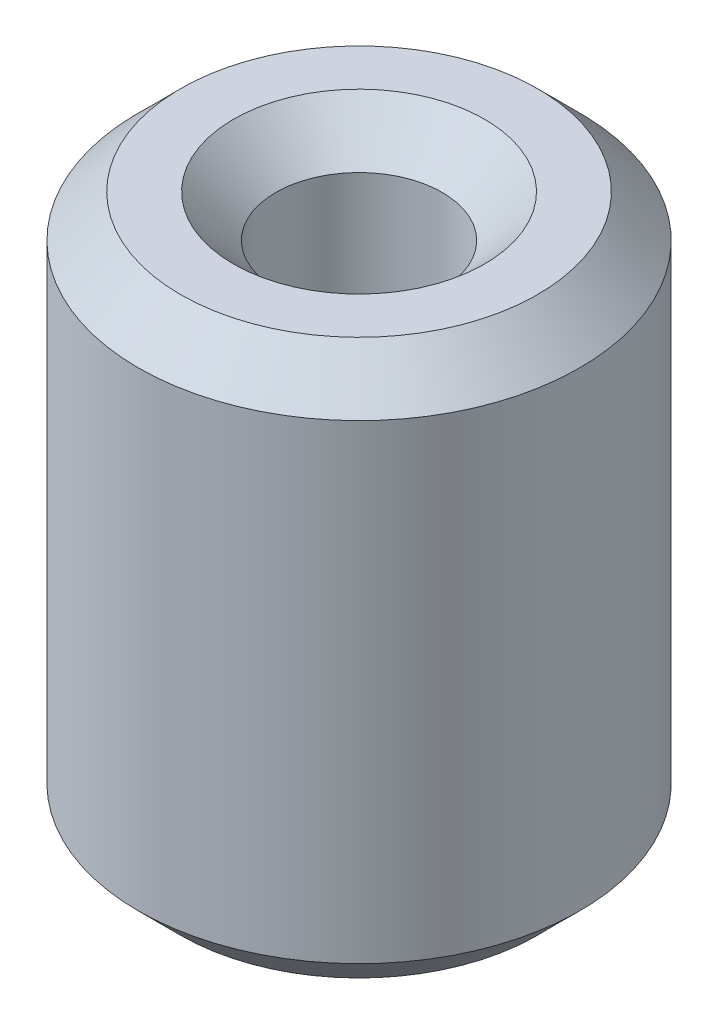
SolidWorks part; units mm, degrees
ref_plane "Front Plane" through (0, 0, 0) normal (0, 0, 1) x (1, 0, 0)
ref_plane "Top Plane" through (0, 0, 0) normal (0, 1, 0) x (1, 0, 0)
ref_plane "Right Plane" through (0, 0, 0) normal (1, 0, 0) x (0, 0, -1)
sketch "Sketch1" plane through (0, 0, 0) normal (0, 1, 0) x (1, 0, 0)
  circle A0 centre (0, 0) radius 15
  dimension "SLEEVE_OD" = 30
extrude "Boss-Extrude1" add sketch "Sketch1" along normal blind 37.7074
sketch "Sketch2" plane through (0, 0, 0) normal (0, 1, 0) x (1, 0, 0)
  circle A0 centre (0, 0) radius 5.656
  dimension "BORE_D" = 11.312
extrude "Cut-Extrude1" cut sketch "Sketch2" along normal through all
chamfer "Chamfer1" distance 2.8733 angle 45 4 edges at (0, 37.7074, 5.656) (0, 0, 5.656) (0, 0, 15) (0, 37.7074, 15)
